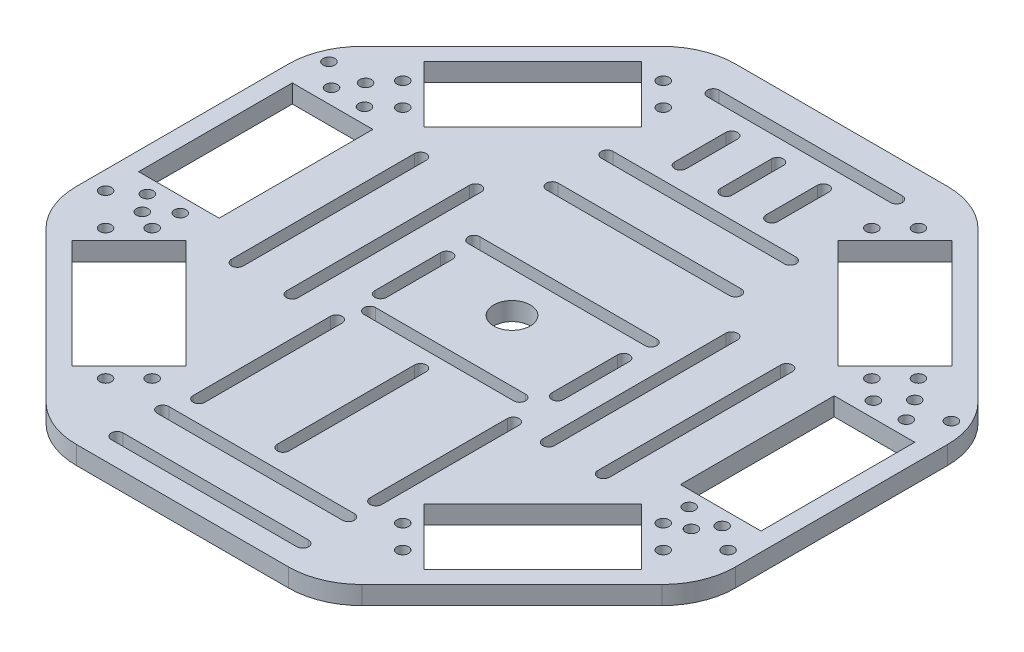
SolidWorks part; units mm, degrees
ref_plane "Front Plane" through (0, 0, 0) normal (0, 0, 1) x (1, 0, 0)
ref_plane "Top Plane" through (0, 0, 0) normal (0, 1, 0) x (1, 0, 0)
ref_plane "Right Plane" through (0, 0, 0) normal (1, 0, 0) x (0, 0, -1)
sketch "Sketch1" plane through (0, 0, 0) normal (0, 1, 0) x (1, 0, 0)
  line L1 (-90, -37.2792) -> (-37.2792, -90)
  line L2 (-37.2792, -90) -> (37.2792, -90)
  line L3 (37.2792, -90) -> (90, -37.2792)
  line L4 (90, -37.2792) -> (90, 37.2792)
  line L5 (90, 37.2792) -> (37.2792, 90)
  line L6 (37.2792, 90) -> (-37.2792, 90)
  line L7 (-37.2792, 90) -> (-90, 37.2792)
  line L8 (-90, 37.2792) -> (-90, -37.2792)
  line L12 (63.6396, -63.6396) -> (0, 0) construction
  line L21 (-20.4, -34.5422) -> (-34.5422, -20.4)
  line L22 (-20.4, -34.5422) -> (-50.0985, -64.2407)
  line L23 (-50.0985, -64.2407) -> (-64.2407, -50.0985)
  line L24 (-34.5422, -20.4) -> (-64.2407, -50.0985)
  line L25 (-38.85, -10) -> (-38.85, 10)
  line L26 (-38.85, -10) -> (-80.85, -10)
  line L27 (-80.85, -10) -> (-80.85, 10)
  line L28 (-38.85, 10) -> (-80.85, 10)
  line L29 (-34.5422, 20.4) -> (-20.4, 34.5422)
  line L30 (-34.5422, 20.4) -> (-64.2407, 50.0985)
  line L31 (-64.2407, 50.0985) -> (-50.0985, 64.2407)
  line L32 (-20.4, 34.5422) -> (-50.0985, 64.2407)
  line L37 (20.4, 34.5422) -> (34.5422, 20.4)
  line L38 (20.4, 34.5422) -> (50.0985, 64.2407)
  line L39 (50.0985, 64.2407) -> (64.2407, 50.0985)
  line L40 (34.5422, 20.4) -> (64.2407, 50.0985)
  line L41 (38.85, 10) -> (38.85, -10)
  line L42 (38.85, 10) -> (80.85, 10)
  line L43 (80.85, 10) -> (80.85, -10)
  line L44 (38.85, -10) -> (80.85, -10)
  circle A0 centre (0, 0) radius 90 construction
  circle A13 centre (0, 0) radius 90 construction
  circle A14 centre (-27.7186, -21.3546) radius 2.5
  circle A15 centre (-21.3546, -27.7186) radius 2.5
  circle A16 centre (-56.9221, -63.2861) radius 2.5
  circle A17 centre (-63.2861, -56.9221) radius 2.5
  circle A18 centre (0, 0) radius 90 construction
  circle A19 centre (-34.7, 4.5) radius 2.5
  circle A20 centre (-34.7, -4.5) radius 2.5
  circle A21 centre (-85, -4.5) radius 2.5
  circle A22 centre (-85, 4.5) radius 2.5
  circle A23 centre (0, 0) radius 90 construction
  circle A24 centre (-21.3546, 27.7186) radius 2.5
  circle A25 centre (-27.7186, 21.3546) radius 2.5
  circle A26 centre (-63.2861, 56.9221) radius 2.5
  circle A27 centre (-56.9221, 63.2861) radius 2.5
  circle A28 centre (0, 0) radius 90 construction
  circle A33 centre (0, 0) radius 90 construction
  circle A34 centre (27.7186, 21.3546) radius 2.5
  circle A35 centre (21.3546, 27.7186) radius 2.5
  circle A36 centre (56.9221, 63.2861) radius 2.5
  circle A37 centre (63.2861, 56.9221) radius 2.5
  circle A38 centre (0, 0) radius 90 construction
  circle A39 centre (34.7, -4.5) radius 2.5
  circle A40 centre (34.7, 4.5) radius 2.5
  circle A41 centre (85, 4.5) radius 2.5
  circle A42 centre (85, -4.5) radius 2.5
  circle A43 centre (0, 0) radius 90 construction
  point P15 (63.6396, -63.6396)
  point P16 (60.1041, -60.1041)
  point P17 (57.1696, -57.1696)
  point P121 (0, 0)
  dimension "D1" = 90
  dimension "D12" = 8
extrude "Baseplate" add sketch "Sketch1" along normal blind 5 contours L7 L8 L1 L2 L3 L4 L5 L6 A42 A41 A40 A39 A37 A36 A35 A34 A27 A26 A25 A24 A22 A21 A20 A19 A17 A16 A15 A14 L44 L41 | L29 L32 L31 L30 | L37 L40 L39 L38 | L41 L44 L43 L42 | L25 L28 L27 L26 | A27 | A26 | A25 | A24 | A22 | A21 | A19 | A20 | A14 | A15 | A17 | A16 | A40 | A41 | A42 | A35 | A34 | A39 | A37 | A36 | L21 L24 L23 L22 region at (1.7472, 0, 1.7472) region at (-59.85, 0, 0) region at (-42.3203, 0, -42.3203) region at (42.3203, 0, -42.3203) region at (59.85, 0, 0) region at (-27.7186, 0, 21.3546) region at (-21.3546, 0, 27.7186) region at (-56.9221, 0, 63.2861) region at (-63.2861, 0, 56.9221) region at (-34.7, 0, -4.5) region at (-34.7, 0, 4.5) region at (-85, 0, 4.5) region at (-85, 0, -4.5) region at (-21.3546, 0, -27.7186) region at (-27.7186, 0, -21.3546) region at (-63.2861, 0, -56.9221) region at (-56.9221, 0, -63.2861) region at (34.7, 0, -4.5) region at (85, 0, -4.5) region at (85, 0, 4.5)
fillet "Fillet1" radius 20 8 edges at (-90, 2.5, -37.2792) (-37.2792, 2.5, -90) (37.2792, 2.5, -90) (90, 2.5, -37.2792) (90, 2.5, 37.2792) (37.2792, 2.5, 90) (-37.2792, 2.5, 90) (-90, 2.5, 37.2792)
sketch "Sketch2" plane through (0, 5, 0) normal (0, 1, 0) x (1, 0, 0)
  line L0 (90, -28.9949) -> (90, 28.9949) construction
  line L1 (63, 25.0051) -> (85, 25.0051)
  line L2 (63, 25.0051) -> (63, -16.9949)
  line L3 (63, -16.9949) -> (85, -16.9949)
  line L4 (85, 25.0051) -> (85, -16.9949)
  circle A0 centre (78.5, 29.2051) radius 1.6
  circle A1 centre (69.5, 29.2051) radius 1.6
  circle A2 centre (69.5, -21.0949) radius 1.6
  circle A3 centre (78.5, -21.0949) radius 1.6
  point P8 (74, 25.0051)
  dimension "D1" = 3.2
  dimension "D2" = 9
  dimension "D3" = 50.3
  dimension "D4" = 22
  dimension "D5" = 42
  dimension "D6" = 4.2
  dimension "D7" = 4.5
  dimension "D8" = 5
  dimension "D9" = 12
extrude "Servo hole" cut sketch "Sketch2" against normal through all contours A0 | L4 L1 L2 L3 | A2 | A3 | A1 region at (74, 5, -4.0051) region at (78.5, 5, -29.2051) region at (69.5, 5, 21.0949) region at (78.5, 5, 21.0949)
sketch "Sketch3" plane through (0, 5, 0) normal (0, 1, 0) x (1, 0, 0)
  circle A0 centre (0, 0) radius 5
  dimension "D1" = 10
extrude "Center hole" cut sketch "Sketch3" against normal through all
pattern_circular "Servo hole pattern" count 8 over 360 about axis through (0, 5, 0) along (0, 1, 0) skipping 2, 3, 4, 5, 6 of "Servo hole"
sketch "Sketch4" plane through (0, 5, 0) normal (0, 1, 0) x (1, 0, 0)
  line L0 (-28.9949, -90) -> (28.9949, -90) construction
  line L1 (-90, 28.9949) -> (-90, -28.9949) construction
  circle A0 centre (-23, 5.1332) radius 1.6
  circle A1 centre (-23, -70) radius 1.6
  circle A2 centre (25.3362, 12.6262) radius 1.6
  circle A3 centre (25.3362, -70) radius 1.6
  circle A4 centre (-7.5585, -18.3745) radius 1.6
  circle A5 centre (20.4577, -18.3745) radius 1.6
  dimension "D1" = 3.2
  dimension "D8" = 20
  dimension "D2" = 7.493
  dimension "D3" = 48.3362
  dimension "D4" = 31.0007
  dimension "D5" = 51.6255
  dimension "D6" = 4.8785
  dimension "D7" = 28.0162
  dimension "D9" = 67
extrude "Arduino Screw holes" cut sketch "Sketch4" against normal through all
ref_plane "Midplane" through (0, 0, 0) normal (1, 0, 0) x (0, 0, -1)
mirror "Mirror1" about plane through (0, 0, 0) normal (1, 0, 0) of "Servo hole pattern", "Servo hole"
sketch "Sketch5" plane through (0, 5, 0) normal (0, 1, 0) x (1, 0, 0)
  line L0 (-25, 36) -> (25, 36) construction
  line L1 (-25, 37.6) -> (25, 37.6)
  line L2 (-25, 34.4) -> (25, 34.4)
  line L3 (-25, 51) -> (25, 51) construction
  line L4 (-25, 52.6) -> (25, 52.6)
  line L5 (-25, 49.4) -> (25, 49.4)
  line L6 (-50, 25) -> (-50, -25) construction
  line L7 (-48.4, 25) -> (-48.4, -25)
  line L8 (-51.6, 25) -> (-51.6, -25)
  line L9 (-35, 25) -> (-35, -25) construction
  line L10 (-33.4, 25) -> (-33.4, -25)
  line L11 (-36.6, 25) -> (-36.6, -25)
  line L12 (35, 25) -> (35, -25) construction
  line L13 (36.6, 25) -> (36.6, -25)
  line L14 (33.4, 25) -> (33.4, -25)
  line L15 (50, 25) -> (50, -25) construction
  line L16 (51.6, 25) -> (51.6, -25)
  line L17 (48.4, 25) -> (48.4, -25)
  line L18 (-25, 80) -> (25, 80) construction
  line L19 (-25, 81.6) -> (25, 81.6)
  line L20 (-25, 78.4) -> (25, 78.4)
  line L21 (-12.5, 72.5) -> (-12.5, 58.5) construction
  line L22 (-10.9, 72.5) -> (-10.9, 58.5)
  line L23 (-14.1, 72.5) -> (-14.1, 58.5)
  line L24 (12.5, 72.5) -> (12.5, 58.5) construction
  line L25 (14.1, 72.5) -> (14.1, 58.5)
  line L26 (10.9, 72.5) -> (10.9, 58.5)
  line L27 (28.9949, 90) -> (-28.9949, 90) construction
  line L28 (0, 72.5) -> (0, 58.5) construction
  line L29 (1.6, 72.5) -> (1.6, 58.5)
  line L30 (-1.6, 72.5) -> (-1.6, 58.5)
  arc A0 (-25, 37.6) -> (-25, 34.4) centre (-25, 36) ccw
  arc A1 (25, 34.4) -> (25, 37.6) centre (25, 36) ccw
  arc A2 (-25, 52.6) -> (-25, 49.4) centre (-25, 51) ccw
  arc A3 (25, 49.4) -> (25, 52.6) centre (25, 51) ccw
  arc A4 (-48.4, 25) -> (-51.6, 25) centre (-50, 25) ccw
  arc A5 (-51.6, -25) -> (-48.4, -25) centre (-50, -25) ccw
  arc A6 (-33.4, 25) -> (-36.6, 25) centre (-35, 25) ccw
  arc A7 (-36.6, -25) -> (-33.4, -25) centre (-35, -25) ccw
  arc A8 (36.6, 25) -> (33.4, 25) centre (35, 25) ccw
  arc A9 (33.4, -25) -> (36.6, -25) centre (35, -25) ccw
  arc A10 (51.6, 25) -> (48.4, 25) centre (50, 25) ccw
  arc A11 (48.4, -25) -> (51.6, -25) centre (50, -25) ccw
  arc A12 (-25, 81.6) -> (-25, 78.4) centre (-25, 80) ccw
  arc A13 (25, 78.4) -> (25, 81.6) centre (25, 80) ccw
  arc A14 (-10.9, 72.5) -> (-14.1, 72.5) centre (-12.5, 72.5) ccw
  arc A15 (-14.1, 58.5) -> (-10.9, 58.5) centre (-12.5, 58.5) ccw
  arc A16 (14.1, 72.5) -> (10.9, 72.5) centre (12.5, 72.5) ccw
  arc A17 (10.9, 58.5) -> (14.1, 58.5) centre (12.5, 58.5) ccw
  arc A18 (1.6, 72.5) -> (-1.6, 72.5) centre (0, 72.5) ccw
  arc A19 (-1.6, 58.5) -> (1.6, 58.5) centre (0, 58.5) ccw
  point P2 (0, 36)
  point P7 (0, 51)
  point P14 (-50, 0)
  point P21 (-35, 0)
  point P28 (35, 0)
  point P35 (50, 0)
  point P42 (0, 80)
  point P48 (-12.5, 65.5)
  point P57 (12.5, 65.5)
  point P64 (0, 65.5)
  dimension "D1" = 1.6
  dimension "D7" = 50
  dimension "D2" = 15
  dimension "D3" = 15
  dimension "D4" = 15
  dimension "D5" = 10
  dimension "D6" = 50
  dimension "D8" = 35
  dimension "D9" = 35
  dimension "D10" = 36
  dimension "D11" = 12.5
  dimension "D12" = 12.5
  dimension "D13" = 7.5
  dimension "D14" = 7.5
extrude "Slits" cut sketch "Sketch5" against normal through all contours L30 A19 L29 A18 | L26 A17 L25 A16 | L5 A3 L4 A2 | L2 A1 L1 A0 | L8 A5 L7 A4 | L11 A7 L10 A6 | L14 A9 L13 A8 | L17 A11 L16 A10 | L19 A13 L20 A12 | L22 A15 L23 A14 region at (0, 5, -36) region at (0, 5, -51) region at (-50, 5, 0) region at (-35, 5, 0) region at (35, 5, 0) region at (50, 5, 0) region at (12.5, 5, -65.5) region at (0, 5, -65.5)
sketch "Sketch6" plane through (0, 5, 0) normal (0, 1, 0) x (1, 0, 0)
  circle A0 centre (-75, 35) radius 1.6
  circle A1 centre (-85, 35) radius 1.6
  dimension "D1" = 3.2
  dimension "D3" = 10
  dimension "D4" = 85
  dimension "D5" = 35
extrude "Exterior Screw Holes" cut sketch "Sketch6" against normal through all
ref_plane "Plane1" through (0, 0, 0) normal (0, 0, 1) x (1, 0, 0)
mirror "Mirror2" about plane through (0, 0, 0) normal (1, 0, 0) of "Exterior Screw Holes"
sketch "Sketch7" plane through (0, 5, 0) normal (0, 1, 0) x (1, 0, 0)
  line L0 (-85, 35) -> (-85, 2.3324)
  circle A0 centre (-85, -26) radius 1.6
  circle A1 centre (-75, -26) radius 1.6
  dimension "D1" = 3.2
  dimension "D3" = 10
  dimension "D4" = 61
extrude "Cut-Extrude1" cut sketch "Sketch7" against normal through all contours A1 | A0 region at (-75, 5, 26)
mirror "Mirror3" about plane through (0, 0, 0) normal (1, 0, 0) of "Cut-Extrude1"
sketch "Sketch8" plane through (0, 5, 0) normal (0, 1, 0) x (1, 0, 0)
  line L0 (20.4577, -18.3745) -> (-20.4577, -18.3745) construction
  line L1 (20.4577, -19.9745) -> (-20.4577, -19.9745)
  line L2 (20.4577, -16.7745) -> (-20.4577, -16.7745)
  line L3 (0, -25.4762) -> (0, 25.4762) construction
  line L4 (25.3362, 12.6262) -> (-23, 12.6262) construction
  line L5 (25.3362, 11.0262) -> (-23, 11.0262)
  line L6 (25.3362, 14.2262) -> (-23, 14.2262)
  line L7 (-23, -12.8668) -> (-23, 5.1332) construction
  line L8 (-24.6, -12.8668) -> (-24.6, 5.1332)
  line L9 (-21.4, -12.8668) -> (-21.4, 5.1332)
  line L10 (25.3362, 5.1332) -> (25.3362, -12.8668) construction
  line L11 (26.9362, 5.1332) -> (26.9362, -12.8668)
  line L12 (23.7362, 5.1332) -> (23.7362, -12.8668)
  line L13 (-25.3362, -70) -> (25.3362, -70) construction
  line L14 (-25.3362, -68.4) -> (25.3362, -68.4)
  line L15 (-25.3362, -71.6) -> (25.3362, -71.6)
  line L16 (-23, -25) -> (-23, -62.5) construction
  line L17 (-21.4, -25) -> (-21.4, -62.5)
  line L18 (-24.6, -25) -> (-24.6, -62.5)
  line L19 (25.3362, -62.5) -> (25.3362, -25) construction
  line L20 (23.7362, -62.5) -> (23.7362, -25)
  line L21 (26.9362, -62.5) -> (26.9362, -25)
  line L22 (0, -62.5) -> (0, -25) construction
  line L23 (-1.6, -62.5) -> (-1.6, -25)
  line L24 (1.6, -62.5) -> (1.6, -25)
  line L25 (-25.3362, -82.5) -> (25.3362, -82.5) construction
  line L26 (-25.3362, -80.9) -> (25.3362, -80.9)
  line L27 (-25.3362, -84.1) -> (25.3362, -84.1)
  arc A0 (20.4577, -19.9745) -> (20.4577, -16.7745) centre (20.4577, -18.3745) ccw
  arc A1 (-20.4577, -16.7745) -> (-20.4577, -19.9745) centre (-20.4577, -18.3745) ccw
  circle A2 centre (-7.5585, -18.3745) radius 1.6 construction
  arc A3 (25.3362, 11.0262) -> (25.3362, 14.2262) centre (25.3362, 12.6262) ccw
  arc A4 (-23, 14.2262) -> (-23, 11.0262) centre (-23, 12.6262) ccw
  arc A5 (-24.6, -12.8668) -> (-21.4, -12.8668) centre (-23, -12.8668) ccw
  arc A6 (-21.4, 5.1332) -> (-24.6, 5.1332) centre (-23, 5.1332) ccw
  arc A7 (26.9362, 5.1332) -> (23.7362, 5.1332) centre (25.3362, 5.1332) ccw
  arc A8 (23.7362, -12.8668) -> (26.9362, -12.8668) centre (25.3362, -12.8668) ccw
  arc A9 (-25.3362, -68.4) -> (-25.3362, -71.6) centre (-25.3362, -70) ccw
  arc A10 (25.3362, -71.6) -> (25.3362, -68.4) centre (25.3362, -70) ccw
  arc A11 (-21.4, -25) -> (-24.6, -25) centre (-23, -25) ccw
  arc A12 (-24.6, -62.5) -> (-21.4, -62.5) centre (-23, -62.5) ccw
  arc A13 (23.7362, -62.5) -> (26.9362, -62.5) centre (25.3362, -62.5) ccw
  arc A14 (26.9362, -25) -> (23.7362, -25) centre (25.3362, -25) ccw
  arc A15 (-1.6, -62.5) -> (1.6, -62.5) centre (0, -62.5) ccw
  arc A16 (1.6, -25) -> (-1.6, -25) centre (0, -25) ccw
  arc A17 (-25.3362, -80.9) -> (-25.3362, -84.1) centre (-25.3362, -82.5) ccw
  arc A18 (25.3362, -84.1) -> (25.3362, -80.9) centre (25.3362, -82.5) ccw
  point P3 (0, -18.3745)
  point P8 (1.1681, 12.6262)
  point P20 (-23, -3.8668)
  point P30 (25.3362, -3.8668)
  point P35 (0, -70)
  point P40 (-23, -43.75)
  point P50 (25.3362, -43.75)
  point P57 (0, -43.75)
  point P65 (0, -82.5)
  point P72 (0, 0)
  point P73 (0, 0)
  point P74 (0, 0)
  point P75 (0, 0)
  dimension "D2" = 1.6
  dimension "D1" = 18
  dimension "D3" = 37.5
  dimension "D4" = 7.5
  dimension "D5" = 12.5
extrude "Cut-Extrude2" cut sketch "Sketch8" against normal through all contours L9 A6 L8 A5 | L12 A8 L11 A7 | L2 A1 L1 A0 | L24 A16 L23 A15 | L21 A14 L20 A13 | L27 A18 L26 A17 | L6 A4 L5 A3 | L17 A12 L18 A11 | L14 A10 L15 A9 region at (0, 5, 18.3745) region at (-23, 5, 3.8668) region at (25.3362, 5, 3.8668) region at (25.3362, 5, 43.75) region at (0, 5, 43.75) region at (0, 5, 82.5)
